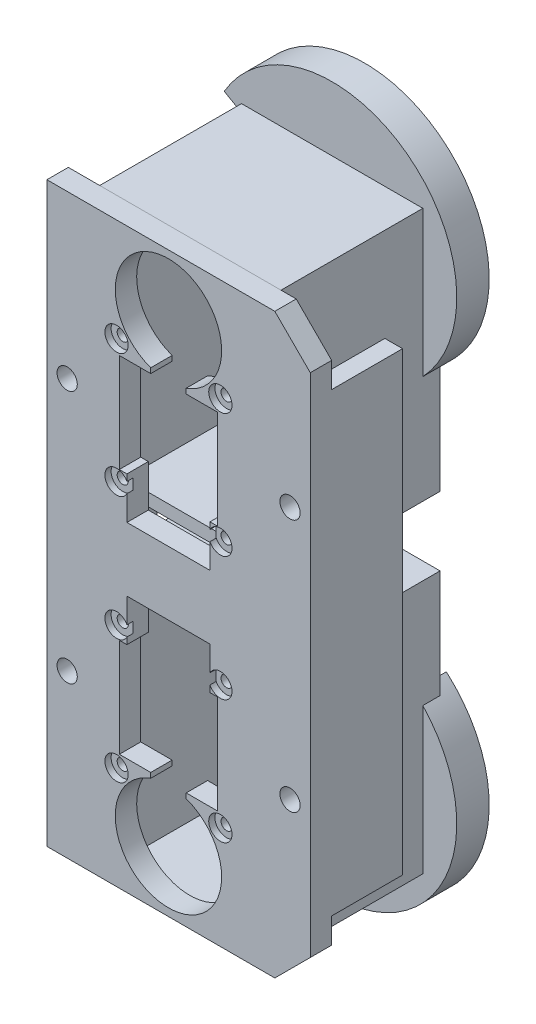
SolidWorks part; units mm, degrees
ref_plane "Front Plane" through (0, 0, 0) normal (0, 0, 1) x (1, 0, 0)
ref_plane "Top Plane" through (0, 0, 0) normal (0, 1, 0) x (1, 0, 0)
ref_plane "Right Plane" through (0, 0, 0) normal (1, 0, 0) x (0, 0, -1)
ref_plane "PZ_p64_700" through (0, 0, 64.7) normal (0, 0, 1) x (1, 0, 0)
sketch "S_prism1" plane through (0, 0, 64.7) normal (0, 0, 1) x (1, 0, 0)
  line L0 (28, -50) -> (28, 50)
  line L1 (28, 50) -> (21, 57)
  line L2 (21, 57) -> (-24, 57)
  line L3 (-24, 57) -> (-24, -57)
  line L4 (-24, -57) -> (21, -57)
  line L5 (21, -57) -> (28, -50)
extrude "Boss_1" add sketch "S_prism1" along normal blind 4.225
ref_plane "PZ_p50_700" through (0, 0, 50.7) normal (0, 0, 1) x (1, 0, 0)
sketch "S_box2" plane through (0, 0, 50.7) normal (0, 0, 1) x (1, 0, 0)
  line L0 (24.5, -45) -> (28, -45)
  line L1 (28, -45) -> (28, 45)
  line L2 (28, 45) -> (24.5, 45)
  line L3 (24.5, 45) -> (24.5, -45)
  dimension "P1" = 24.5
  dimension "P2" = 45
  dimension "P3" = 28
  dimension "P4" = 45
  dimension "P5" = 28
  dimension "P6" = 45
  dimension "P7" = 24.5
  dimension "P8" = 45
extrude "Boss_2" add sketch "S_box2" along normal blind 14.5
sketch "S_box3" plane through (0, 0, 50.7) normal (0, 0, 1) x (1, 0, 0)
  line L0 (-24, -45) -> (-20.5, -45)
  line L1 (-20.5, -45) -> (-20.5, 45)
  line L2 (-20.5, 45) -> (-24, 45)
  line L3 (-24, 45) -> (-24, -45)
  dimension "P1" = 24
  dimension "P2" = 45
  dimension "P3" = 20.5
  dimension "P4" = 45
  dimension "P5" = 20.5
  dimension "P6" = 45
  dimension "P7" = 24
  dimension "P8" = 45
extrude "Boss_3" add sketch "S_box3" along normal blind 14.5
ref_plane "PZ_p33_200" through (0, 0, 33.2) normal (0, 0, 1) x (1, 0, 0)
sketch "S_box4" plane through (0, 0, 33.2) normal (0, 0, 1) x (1, 0, 0)
  line L0 (-17.9, 6.8) -> (17.9, 6.8)
  line L1 (17.9, 6.8) -> (17.9, 9.3)
  line L2 (17.9, 9.3) -> (-17.9, 9.3)
  line L3 (-17.9, 9.3) -> (-17.9, 6.8)
  dimension "P1" = 17.9
  dimension "P2" = 6.8
  dimension "P3" = 17.9
  dimension "P4" = 6.8
  dimension "P5" = 17.9
  dimension "P6" = 9.3
  dimension "P7" = 17.9
  dimension "P8" = 9.3
extrude "Boss_4" add sketch "S_box4" along normal blind 35.725
sketch "S_box5" plane through (0, 0, 33.2) normal (0, 0, 1) x (1, 0, 0)
  line L0 (-17.9, 55.7) -> (17.9, 55.7)
  line L1 (17.9, 55.7) -> (17.9, 56.9)
  line L2 (17.9, 56.9) -> (-17.9, 56.9)
  line L3 (-17.9, 56.9) -> (-17.9, 55.7)
  dimension "P1" = 17.9
  dimension "P2" = 55.7
  dimension "P3" = 17.9
  dimension "P4" = 55.7
  dimension "P5" = 17.9
  dimension "P6" = 56.9
  dimension "P7" = 17.9
  dimension "P8" = 56.9
extrude "Boss_5" add sketch "S_box5" along normal blind 35.725
sketch "S_box6" plane through (0, 0, 33.2) normal (0, 0, 1) x (1, 0, 0)
  line L0 (-17.9, 6.8) -> (-12.9, 6.8)
  line L1 (-12.9, 6.8) -> (-12.9, 56.9)
  line L2 (-12.9, 56.9) -> (-17.9, 56.9)
  line L3 (-17.9, 56.9) -> (-17.9, 6.8)
  dimension "P1" = 17.9
  dimension "P2" = 6.8
  dimension "P3" = 12.9
  dimension "P4" = 6.8
  dimension "P5" = 12.9
  dimension "P6" = 56.9
  dimension "P7" = 17.9
  dimension "P8" = 56.9
extrude "Boss_6" add sketch "S_box6" along normal blind 35.725
sketch "S_box7" plane through (0, 0, 33.2) normal (0, 0, 1) x (1, 0, 0)
  line L0 (12.9, 6.8) -> (17.9, 6.8)
  line L1 (17.9, 6.8) -> (17.9, 56.9)
  line L2 (17.9, 56.9) -> (12.9, 56.9)
  line L3 (12.9, 56.9) -> (12.9, 6.8)
  dimension "P1" = 12.9
  dimension "P2" = 6.8
  dimension "P3" = 17.9
  dimension "P4" = 6.8
  dimension "P5" = 17.9
  dimension "P6" = 56.9
  dimension "P7" = 12.9
  dimension "P8" = 56.9
extrude "Boss_7" add sketch "S_box7" along normal blind 35.725
sketch "S_box8" plane through (0, 0, 64.7) normal (0, 0, 1) x (1, 0, 0)
  line L0 (-17.9, 6.8) -> (17.9, 6.8)
  line L1 (17.9, 6.8) -> (17.9, 56.9)
  line L2 (17.9, 56.9) -> (-17.9, 56.9)
  line L3 (-17.9, 56.9) -> (-17.9, 6.8)
  dimension "P1" = 17.9
  dimension "P2" = 6.8
  dimension "P3" = 17.9
  dimension "P4" = 6.8
  dimension "P5" = 17.9
  dimension "P6" = 56.9
  dimension "P7" = 17.9
  dimension "P8" = 56.9
extrude "Boss_8" add sketch "S_box8" along normal blind 4.225
ref_plane "PZ_p30_100" through (0, 0, 30.1) normal (0, 0, 1) x (1, 0, 0)
sketch "S_cyl9" plane through (0, 0, 30.1) normal (0, 0, 1) x (1, 0, 0)
  circle A0 centre (0, 45) radius 19
  dimension "D1_S_cyl9" = 38
  dimension "P2" = 45
extrude "Boss_9" add sketch "S_cyl9" along normal blind 2.6
ref_plane "PZ_p30_200" through (0, 0, 30.2) normal (0, 0, 1) x (1, 0, 0)
sketch "S_prism10" plane through (0, 0, 30.2) normal (0, 0, 1) x (1, 0, 0)
  line L0 (-21.3042, 57.3) -> (-9.5263, 50.5)
  line L1 (7.2166, 36.6982) -> (16.1391, 26.4341)
  arc A0 (16.1391, 26.4341) -> (-21.3042, 57.3) centre (0, 45) ccw
  arc A1 (-9.5263, 50.5) -> (7.2166, 36.6982) centre (0, 45) cw
extrude "Boss_10" add sketch "S_prism10" along normal blind 6.4
sketch "S_box11" plane through (0, 0, 33.2) normal (0, 0, 1) x (1, 0, 0)
  line L0 (-17.9, -56.9) -> (17.9, -56.9)
  line L1 (17.9, -56.9) -> (17.9, -55.7)
  line L2 (17.9, -55.7) -> (-17.9, -55.7)
  line L3 (-17.9, -55.7) -> (-17.9, -56.9)
  dimension "P1" = 17.9
  dimension "P2" = 56.9
  dimension "P3" = 17.9
  dimension "P4" = 56.9
  dimension "P5" = 17.9
  dimension "P6" = 55.7
  dimension "P7" = 17.9
  dimension "P8" = 55.7
extrude "Boss_11" add sketch "S_box11" along normal blind 35.725
sketch "S_box12" plane through (0, 0, 33.2) normal (0, 0, 1) x (1, 0, 0)
  line L0 (-17.9, -9.3) -> (17.9, -9.3)
  line L1 (17.9, -9.3) -> (17.9, -6.8)
  line L2 (17.9, -6.8) -> (-17.9, -6.8)
  line L3 (-17.9, -6.8) -> (-17.9, -9.3)
  dimension "P1" = 17.9
  dimension "P2" = 9.3
  dimension "P3" = 17.9
  dimension "P4" = 9.3
  dimension "P5" = 17.9
  dimension "P6" = 6.8
  dimension "P7" = 17.9
  dimension "P8" = 6.8
extrude "Boss_12" add sketch "S_box12" along normal blind 35.725
sketch "S_box13" plane through (0, 0, 33.2) normal (0, 0, 1) x (1, 0, 0)
  line L0 (-17.9, -56.9) -> (-12.9, -56.9)
  line L1 (-12.9, -56.9) -> (-12.9, -6.8)
  line L2 (-12.9, -6.8) -> (-17.9, -6.8)
  line L3 (-17.9, -6.8) -> (-17.9, -56.9)
  dimension "P1" = 17.9
  dimension "P2" = 56.9
  dimension "P3" = 12.9
  dimension "P4" = 56.9
  dimension "P5" = 12.9
  dimension "P6" = 6.8
  dimension "P7" = 17.9
  dimension "P8" = 6.8
extrude "Boss_13" add sketch "S_box13" along normal blind 35.725
sketch "S_box14" plane through (0, 0, 33.2) normal (0, 0, 1) x (1, 0, 0)
  line L0 (12.9, -56.9) -> (17.9, -56.9)
  line L1 (17.9, -56.9) -> (17.9, -6.8)
  line L2 (17.9, -6.8) -> (12.9, -6.8)
  line L3 (12.9, -6.8) -> (12.9, -56.9)
  dimension "P1" = 12.9
  dimension "P2" = 56.9
  dimension "P3" = 17.9
  dimension "P4" = 56.9
  dimension "P5" = 17.9
  dimension "P6" = 6.8
  dimension "P7" = 12.9
  dimension "P8" = 6.8
extrude "Boss_14" add sketch "S_box14" along normal blind 35.725
sketch "S_box15" plane through (0, 0, 64.7) normal (0, 0, 1) x (1, 0, 0)
  line L0 (-17.9, -56.9) -> (17.9, -56.9)
  line L1 (17.9, -56.9) -> (17.9, -6.8)
  line L2 (17.9, -6.8) -> (-17.9, -6.8)
  line L3 (-17.9, -6.8) -> (-17.9, -56.9)
  dimension "P1" = 17.9
  dimension "P2" = 56.9
  dimension "P3" = 17.9
  dimension "P4" = 56.9
  dimension "P5" = 17.9
  dimension "P6" = 6.8
  dimension "P7" = 17.9
  dimension "P8" = 6.8
extrude "Boss_15" add sketch "S_box15" along normal blind 4.225
sketch "S_cyl16" plane through (0, 0, 30.1) normal (0, 0, 1) x (1, 0, 0)
  circle A0 centre (0, -45) radius 19
  dimension "D1_S_cyl16" = 38
  dimension "P2" = 45
extrude "Boss_16" add sketch "S_cyl16" along normal blind 2.6
sketch "S_prism17" plane through (0, 0, 30.2) normal (0, 0, 1) x (1, 0, 0)
  line L0 (16.1391, -26.4341) -> (7.2166, -36.6982)
  line L1 (-9.5263, -50.5) -> (-21.3042, -57.3)
  arc A0 (-21.3042, -57.3) -> (16.1391, -26.4341) centre (0, -45) ccw
  arc A1 (7.2166, -36.6982) -> (-9.5263, -50.5) centre (0, -45) cw
extrude "Boss_17" add sketch "S_prism17" along normal blind 6.4
ref_plane "PZ_p64_600" through (0, 0, 64.6) normal (0, 0, 1) x (1, 0, 0)
sketch "S_hole18" plane through (0, 0, 64.6) normal (0, 0, 1) x (1, 0, 0)
  circle A0 centre (0, 45) radius 10.5
  dimension "D1_S_hole18" = 21
  dimension "P2" = 45
extrude "Hole_18" cut sketch "S_hole18" along normal blind 4.425
ref_plane "PZ_p64_650" through (0, 0, 64.65) normal (0, 0, 1) x (1, 0, 0)
sketch "S_cut19" plane through (0, 0, 64.65) normal (0, 0, 1) x (1, 0, 0)
  line L0 (-9.7, 14.6) -> (9.7, 14.6)
  line L1 (9.7, 14.6) -> (9.7, 34.1)
  line L2 (9.7, 34.1) -> (-9.7, 34.1)
  line L3 (-9.7, 34.1) -> (-9.7, 14.6)
  dimension "P1" = 9.7
  dimension "P2" = 14.6
  dimension "P3" = 9.7
  dimension "P4" = 14.6
  dimension "P5" = 9.7
  dimension "P6" = 34.1
  dimension "P7" = 9.7
  dimension "P8" = 34.1
extrude "Pocket_19" cut sketch "S_cut19" along normal blind 4.375
sketch "S_cut20" plane through (0, 0, 64.65) normal (0, 0, 1) x (1, 0, 0)
  line L0 (-8.2, 6.3) -> (8.2, 6.3)
  line L1 (8.2, 6.3) -> (8.2, 14.6)
  line L2 (8.2, 14.6) -> (-8.2, 14.6)
  line L3 (-8.2, 14.6) -> (-8.2, 6.3)
  dimension "P1" = 8.2
  dimension "P2" = 6.3
  dimension "P3" = 8.2
  dimension "P4" = 6.3
  dimension "P5" = 8.2
  dimension "P6" = 14.6
  dimension "P7" = 8.2
  dimension "P8" = 14.6
extrude "Pocket_20" cut sketch "S_cut20" along normal blind 4.375
sketch "S_cut21" plane through (0, 0, 64.65) normal (0, 0, 1) x (1, 0, 0)
  line L0 (-3.5, 34) -> (3.5, 34)
  line L1 (3.5, 34) -> (3.5, 45)
  line L2 (3.5, 45) -> (-3.5, 45)
  line L3 (-3.5, 45) -> (-3.5, 34)
  dimension "P1" = 3.5
  dimension "P2" = 34
  dimension "P3" = 3.5
  dimension "P4" = 34
  dimension "P5" = 3.5
  dimension "P6" = 45
  dimension "P7" = 3.5
  dimension "P8" = 45
extrude "Pocket_21" cut sketch "S_cut21" along normal blind 4.375
sketch "S_hole22" plane through (0, 0, 64.6) normal (0, 0, 1) x (1, 0, 0)
  circle A0 centre (-10.25, 36.7) radius 1.1
  dimension "D1_S_hole22" = 2.2
  dimension "P2" = 10.25
  dimension "P3" = 36.7
extrude "Hole_22" cut sketch "S_hole22" along normal blind 4.425
ref_plane "PZ_p67_700" through (0, 0, 67.7) normal (0, 0, 1) x (1, 0, 0)
sketch "S_hole23" plane through (0, 0, 67.7) normal (0, 0, 1) x (1, 0, 0)
  circle A0 centre (-10.25, 36.7) radius 2.3
  dimension "D1_S_hole23" = 4.6
  dimension "P2" = 10.25
  dimension "P3" = 36.7
extrude "Hole_23" cut sketch "S_hole23" along normal blind 1.325
sketch "S_hole24" plane through (0, 0, 64.6) normal (0, 0, 1) x (1, 0, 0)
  circle A0 centre (10.25, 36.7) radius 1.1
  dimension "D1_S_hole24" = 2.2
  dimension "P2" = 10.25
  dimension "P3" = 36.7
extrude "Hole_24" cut sketch "S_hole24" along normal blind 4.425
sketch "S_hole25" plane through (0, 0, 67.7) normal (0, 0, 1) x (1, 0, 0)
  circle A0 centre (10.25, 36.7) radius 2.3
  dimension "D1_S_hole25" = 4.6
  dimension "P2" = 10.25
  dimension "P3" = 36.7
extrude "Hole_25" cut sketch "S_hole25" along normal blind 1.325
sketch "S_hole26" plane through (0, 0, 64.6) normal (0, 0, 1) x (1, 0, 0)
  circle A0 centre (-10.25, 12.25) radius 1.1
  dimension "D1_S_hole26" = 2.2
  dimension "P2" = 10.25
  dimension "P3" = 12.25
extrude "Hole_26" cut sketch "S_hole26" along normal blind 4.425
sketch "S_hole27" plane through (0, 0, 67.7) normal (0, 0, 1) x (1, 0, 0)
  circle A0 centre (-10.25, 12.25) radius 2.3
  dimension "D1_S_hole27" = 4.6
  dimension "P2" = 10.25
  dimension "P3" = 12.25
extrude "Hole_27" cut sketch "S_hole27" along normal blind 1.325
sketch "S_hole28" plane through (0, 0, 64.6) normal (0, 0, 1) x (1, 0, 0)
  circle A0 centre (10.25, 12.25) radius 1.1
  dimension "D1_S_hole28" = 2.2
  dimension "P2" = 10.25
  dimension "P3" = 12.25
extrude "Hole_28" cut sketch "S_hole28" along normal blind 4.425
sketch "S_hole29" plane through (0, 0, 67.7) normal (0, 0, 1) x (1, 0, 0)
  circle A0 centre (10.25, 12.25) radius 2.3
  dimension "D1_S_hole29" = 4.6
  dimension "P2" = 10.25
  dimension "P3" = 12.25
extrude "Hole_29" cut sketch "S_hole29" along normal blind 1.325
ref_plane "PZ_p30_050" through (0, 0, 30.05) normal (0, 0, 1) x (1, 0, 0)
sketch "S_cut30" plane through (0, 0, 30.05) normal (0, 0, 1) x (1, 0, 0)
  line L0 (-12.9, 9.3) -> (12.9, 9.3)
  line L1 (12.9, 9.3) -> (12.9, 55.7)
  line L2 (12.9, 55.7) -> (-12.9, 55.7)
  line L3 (-12.9, 55.7) -> (-12.9, 9.3)
  dimension "P1" = 12.9
  dimension "P2" = 9.3
  dimension "P3" = 12.9
  dimension "P4" = 9.3
  dimension "P5" = 12.9
  dimension "P6" = 55.7
  dimension "P7" = 12.9
  dimension "P8" = 55.7
extrude "Pocket_30" cut sketch "S_cut30" along normal blind 6.65
sketch "S_hole31" plane through (0, 0, 30.1) normal (0, 0, 1) x (1, 0, 0)
  circle A0 centre (0, 45) radius 11.5
  dimension "D1_S_hole31" = 23
  dimension "P2" = 45
extrude "Hole_31" cut sketch "S_hole31" along normal blind 3.2
sketch "S_hole32" plane through (0, 0, 30.1) normal (0, 0, 1) x (1, 0, 0)
  circle A0 centre (19.9388, 35.7024) radius 0.9
  dimension "D1_S_hole32" = 1.8
  dimension "P2" = 19.9388
  dimension "P3" = 35.7024
extrude "Hole_32" cut sketch "S_hole32" along normal blind 5.7
sketch "S_hole33" plane through (0, 0, 30.1) normal (0, 0, 1) x (1, 0, 0)
  circle A0 centre (21.2504, 50.694) radius 0.9
  dimension "D1_S_hole33" = 1.8
  dimension "P2" = 21.2504
  dimension "P3" = 50.694
extrude "Hole_33" cut sketch "S_hole33" along normal blind 5.7
sketch "S_hole34" plane through (0, 0, 30.1) normal (0, 0, 1) x (1, 0, 0)
  circle A0 centre (12.6187, 63.0213) radius 0.9
  dimension "D1_S_hole34" = 1.8
  dimension "P2" = 12.6187
  dimension "P3" = 63.0213
extrude "Hole_34" cut sketch "S_hole34" along normal blind 5.7
sketch "S_hole35" plane through (0, 0, 30.1) normal (0, 0, 1) x (1, 0, 0)
  circle A0 centre (0.7678, 66.9866) radius 0.9
  dimension "D1_S_hole35" = 1.8
  dimension "P2" = 0.7678
  dimension "P3" = 66.9866
extrude "Hole_35" cut sketch "S_hole35" along normal blind 5.7
sketch "S_hole36" plane through (0, 0, 64.6) normal (0, 0, 1) x (1, 0, 0)
  circle A0 centre (0, -45) radius 10.5
  dimension "D1_S_hole36" = 21
  dimension "P2" = 45
extrude "Hole_36" cut sketch "S_hole36" along normal blind 4.425
sketch "S_cut37" plane through (0, 0, 64.65) normal (0, 0, 1) x (1, 0, 0)
  line L0 (-9.7, -34.1) -> (9.7, -34.1)
  line L1 (9.7, -34.1) -> (9.7, -14.6)
  line L2 (9.7, -14.6) -> (-9.7, -14.6)
  line L3 (-9.7, -14.6) -> (-9.7, -34.1)
  dimension "P1" = 9.7
  dimension "P2" = 34.1
  dimension "P3" = 9.7
  dimension "P4" = 34.1
  dimension "P5" = 9.7
  dimension "P6" = 14.6
  dimension "P7" = 9.7
  dimension "P8" = 14.6
extrude "Pocket_37" cut sketch "S_cut37" along normal blind 4.375
sketch "S_cut38" plane through (0, 0, 64.65) normal (0, 0, 1) x (1, 0, 0)
  line L0 (-8.2, -14.6) -> (8.2, -14.6)
  line L1 (8.2, -14.6) -> (8.2, -6.3)
  line L2 (8.2, -6.3) -> (-8.2, -6.3)
  line L3 (-8.2, -6.3) -> (-8.2, -14.6)
  dimension "P1" = 8.2
  dimension "P2" = 14.6
  dimension "P3" = 8.2
  dimension "P4" = 14.6
  dimension "P5" = 8.2
  dimension "P6" = 6.3
  dimension "P7" = 8.2
  dimension "P8" = 6.3
extrude "Pocket_38" cut sketch "S_cut38" along normal blind 4.375
sketch "S_cut39" plane through (0, 0, 64.65) normal (0, 0, 1) x (1, 0, 0)
  line L0 (-3.5, -45) -> (3.5, -45)
  line L1 (3.5, -45) -> (3.5, -34)
  line L2 (3.5, -34) -> (-3.5, -34)
  line L3 (-3.5, -34) -> (-3.5, -45)
  dimension "P1" = 3.5
  dimension "P2" = 45
  dimension "P3" = 3.5
  dimension "P4" = 45
  dimension "P5" = 3.5
  dimension "P6" = 34
  dimension "P7" = 3.5
  dimension "P8" = 34
extrude "Pocket_39" cut sketch "S_cut39" along normal blind 4.375
sketch "S_hole40" plane through (0, 0, 64.6) normal (0, 0, 1) x (1, 0, 0)
  circle A0 centre (-10.25, -36.7) radius 1.1
  dimension "D1_S_hole40" = 2.2
  dimension "P2" = 10.25
  dimension "P3" = 36.7
extrude "Hole_40" cut sketch "S_hole40" along normal blind 4.425
sketch "S_hole41" plane through (0, 0, 67.7) normal (0, 0, 1) x (1, 0, 0)
  circle A0 centre (-10.25, -36.7) radius 2.3
  dimension "D1_S_hole41" = 4.6
  dimension "P2" = 10.25
  dimension "P3" = 36.7
extrude "Hole_41" cut sketch "S_hole41" along normal blind 1.325
sketch "S_hole42" plane through (0, 0, 64.6) normal (0, 0, 1) x (1, 0, 0)
  circle A0 centre (10.25, -36.7) radius 1.1
  dimension "D1_S_hole42" = 2.2
  dimension "P2" = 10.25
  dimension "P3" = 36.7
extrude "Hole_42" cut sketch "S_hole42" along normal blind 4.425
sketch "S_hole43" plane through (0, 0, 67.7) normal (0, 0, 1) x (1, 0, 0)
  circle A0 centre (10.25, -36.7) radius 2.3
  dimension "D1_S_hole43" = 4.6
  dimension "P2" = 10.25
  dimension "P3" = 36.7
extrude "Hole_43" cut sketch "S_hole43" along normal blind 1.325
sketch "S_hole44" plane through (0, 0, 64.6) normal (0, 0, 1) x (1, 0, 0)
  circle A0 centre (-10.25, -12.25) radius 1.1
  dimension "D1_S_hole44" = 2.2
  dimension "P2" = 10.25
  dimension "P3" = 12.25
extrude "Hole_44" cut sketch "S_hole44" along normal blind 4.425
sketch "S_hole45" plane through (0, 0, 67.7) normal (0, 0, 1) x (1, 0, 0)
  circle A0 centre (-10.25, -12.25) radius 2.3
  dimension "D1_S_hole45" = 4.6
  dimension "P2" = 10.25
  dimension "P3" = 12.25
extrude "Hole_45" cut sketch "S_hole45" along normal blind 1.325
sketch "S_hole46" plane through (0, 0, 64.6) normal (0, 0, 1) x (1, 0, 0)
  circle A0 centre (10.25, -12.25) radius 1.1
  dimension "D1_S_hole46" = 2.2
  dimension "P2" = 10.25
  dimension "P3" = 12.25
extrude "Hole_46" cut sketch "S_hole46" along normal blind 4.425
sketch "S_hole47" plane through (0, 0, 67.7) normal (0, 0, 1) x (1, 0, 0)
  circle A0 centre (10.25, -12.25) radius 2.3
  dimension "D1_S_hole47" = 4.6
  dimension "P2" = 10.25
  dimension "P3" = 12.25
extrude "Hole_47" cut sketch "S_hole47" along normal blind 1.325
sketch "S_cut48" plane through (0, 0, 30.05) normal (0, 0, 1) x (1, 0, 0)
  line L0 (-12.9, -55.7) -> (12.9, -55.7)
  line L1 (12.9, -55.7) -> (12.9, -9.3)
  line L2 (12.9, -9.3) -> (-12.9, -9.3)
  line L3 (-12.9, -9.3) -> (-12.9, -55.7)
  dimension "P1" = 12.9
  dimension "P2" = 55.7
  dimension "P3" = 12.9
  dimension "P4" = 55.7
  dimension "P5" = 12.9
  dimension "P6" = 9.3
  dimension "P7" = 12.9
  dimension "P8" = 9.3
extrude "Pocket_48" cut sketch "S_cut48" along normal blind 6.65
sketch "S_hole49" plane through (0, 0, 30.1) normal (0, 0, 1) x (1, 0, 0)
  circle A0 centre (0, -45) radius 11.5
  dimension "D1_S_hole49" = 23
  dimension "P2" = 45
extrude "Hole_49" cut sketch "S_hole49" along normal blind 3.2
sketch "S_hole50" plane through (0, 0, 30.1) normal (0, 0, 1) x (1, 0, 0)
  circle A0 centre (19.9388, -35.7024) radius 0.9
  dimension "D1_S_hole50" = 1.8
  dimension "P2" = 19.9388
  dimension "P3" = 35.7024
extrude "Hole_50" cut sketch "S_hole50" along normal blind 5.7
sketch "S_hole51" plane through (0, 0, 30.1) normal (0, 0, 1) x (1, 0, 0)
  circle A0 centre (21.2504, -50.694) radius 0.9
  dimension "D1_S_hole51" = 1.8
  dimension "P2" = 21.2504
  dimension "P3" = 50.694
extrude "Hole_51" cut sketch "S_hole51" along normal blind 5.7
sketch "S_hole52" plane through (0, 0, 30.1) normal (0, 0, 1) x (1, 0, 0)
  circle A0 centre (12.6187, -63.0213) radius 0.9
  dimension "D1_S_hole52" = 1.8
  dimension "P2" = 12.6187
  dimension "P3" = 63.0213
extrude "Hole_52" cut sketch "S_hole52" along normal blind 5.7
sketch "S_hole53" plane through (0, 0, 30.1) normal (0, 0, 1) x (1, 0, 0)
  circle A0 centre (0.7678, -66.9866) radius 0.9
  dimension "D1_S_hole53" = 1.8
  dimension "P2" = 0.7678
  dimension "P3" = 66.9866
extrude "Hole_53" cut sketch "S_hole53" along normal blind 5.7
sketch "S_hole54" plane through (0, 0, 64.6) normal (0, 0, 1) x (1, 0, 0)
  circle A0 centre (-20, -25) radius 2
  dimension "D1_S_hole54" = 4
  dimension "P2" = 20
  dimension "P3" = 25
extrude "Hole_54" cut sketch "S_hole54" along normal blind 4.425
ref_plane "PZ_p60_700" through (0, 0, 60.7) normal (0, 0, 1) x (1, 0, 0)
sketch "S_hole55" plane through (0, 0, 60.7) normal (0, 0, 1) x (1, 0, 0)
  circle A0 centre (-20, -25) radius 1.7
  dimension "D1_S_hole55" = 3.4
  dimension "P2" = 20
  dimension "P3" = 25
extrude "Hole_55" cut sketch "S_hole55" along normal blind 4.1
sketch "S_hole56" plane through (0, 0, 64.6) normal (0, 0, 1) x (1, 0, 0)
  circle A0 centre (-20, 25) radius 2
  dimension "D1_S_hole56" = 4
  dimension "P2" = 20
  dimension "P3" = 25
extrude "Hole_56" cut sketch "S_hole56" along normal blind 4.425
sketch "S_hole57" plane through (0, 0, 60.7) normal (0, 0, 1) x (1, 0, 0)
  circle A0 centre (-20, 25) radius 1.7
  dimension "D1_S_hole57" = 3.4
  dimension "P2" = 20
  dimension "P3" = 25
extrude "Hole_57" cut sketch "S_hole57" along normal blind 4.1
sketch "S_hole58" plane through (0, 0, 64.6) normal (0, 0, 1) x (1, 0, 0)
  circle A0 centre (24, -25) radius 2
  dimension "D1_S_hole58" = 4
  dimension "P2" = 24
  dimension "P3" = 25
extrude "Hole_58" cut sketch "S_hole58" along normal blind 4.425
sketch "S_hole59" plane through (0, 0, 60.7) normal (0, 0, 1) x (1, 0, 0)
  circle A0 centre (24, -25) radius 1.7
  dimension "D1_S_hole59" = 3.4
  dimension "P2" = 24
  dimension "P3" = 25
extrude "Hole_59" cut sketch "S_hole59" along normal blind 4.1
sketch "S_hole60" plane through (0, 0, 64.6) normal (0, 0, 1) x (1, 0, 0)
  circle A0 centre (24, 25) radius 2
  dimension "D1_S_hole60" = 4
  dimension "P2" = 24
  dimension "P3" = 25
extrude "Hole_60" cut sketch "S_hole60" along normal blind 4.425
sketch "S_hole61" plane through (0, 0, 60.7) normal (0, 0, 1) x (1, 0, 0)
  circle A0 centre (24, 25) radius 1.7
  dimension "D1_S_hole61" = 3.4
  dimension "P2" = 24
  dimension "P3" = 25
extrude "Hole_61" cut sketch "S_hole61" along normal blind 4.1
equation "\"plate_t\" = 3"
equation "\"clearance\" = 0.5"
